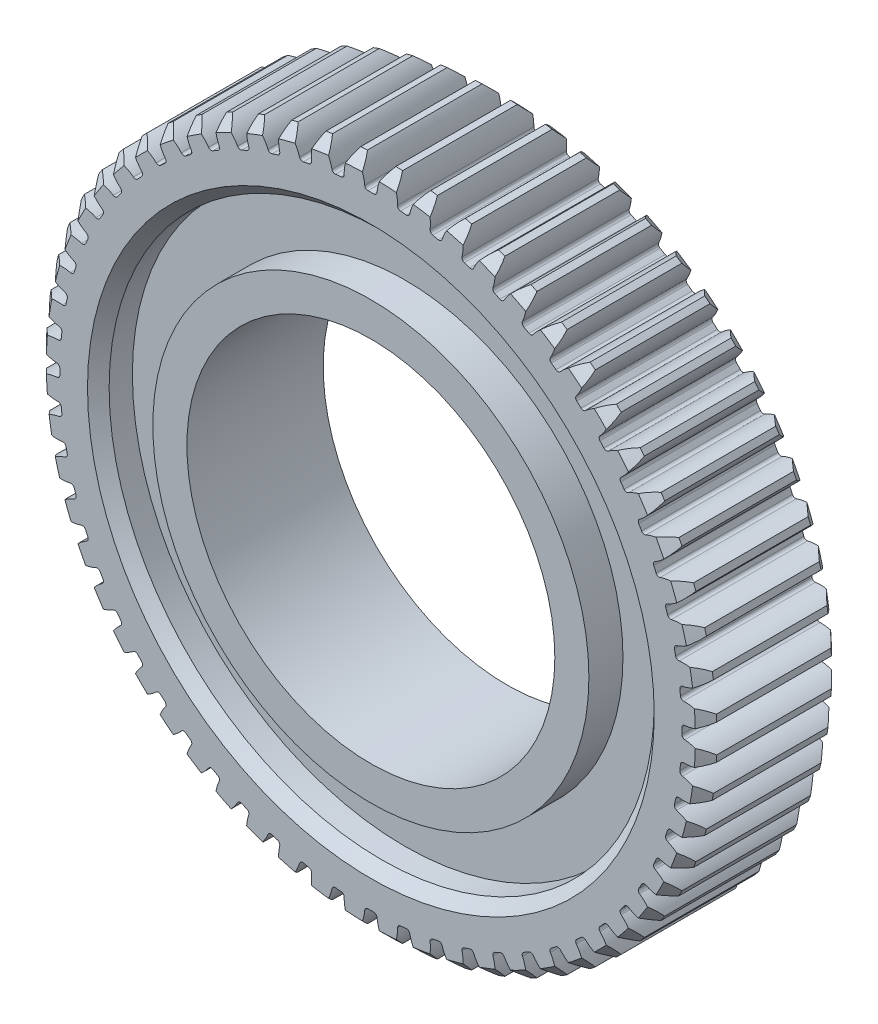
SolidWorks part; units mm, degrees
ref_plane "Front Plane" through (0, 0, 0) normal (0, 0, 1) x (1, 0, 0)
ref_plane "Top Plane" through (0, 0, 0) normal (0, 1, 0) x (1, 0, 0)
ref_plane "Right Plane" through (0, 0, 0) normal (1, 0, 0) x (0, 0, -1)
sketch "Sketch1" plane through (0, 0, 0) normal (0, 0, 1) x (1, 0, 0)
  circle A0 centre (0, 0) radius 47.625 construction
  circle A1 centre (0, 0) radius 49.2125
  dimension "D1" = 95.25
  dimension "D2" = 98.425
extrude "Boss-Extrude1" add sketch "Sketch1" along normal mid plane 20
sketch "Sketch2" plane through (0, 0, 0) normal (0, 0, 1) x (1, 0, 0)
  line L0 (0, 49.2125) -> (0, 0) construction
  line L1 (0, 0) -> (5.1441, 48.9429) construction
  line L2 (0, 0) -> (2.5756, 49.1451) construction
  line L3 (0, 0) -> (-0.8785, 45.6322) construction
  line L4 (-1.2467, 47.6087) -> (1.2467, 47.6087) construction
  line L5 (1.2467, 47.6087) -> (3.7366, 47.4782) construction
  line L6 (-1.8182, 49.1789) -> (0, 44.1835) construction
  circle A0 centre (0, 0) radius 46.0375 construction
  arc A2 (0.8785, 45.6322) -> (-0.8785, 45.6322) centre (0, 0) ccw
  circle A3 centre (0, 0) radius 49.2125 construction
  arc A4 (-0.8785, 45.6322) -> (-2.087, 49.1682) centre (-7.0009, 45.5143) ccw
  arc A5 (0.8785, 45.6322) -> (2.087, 49.1682) centre (7.0009, 45.5143) cw
  circle A6 centre (0, 0) radius 47.625 construction
  circle A7 centre (0, 0) radius 49.2125 construction
  arc A8 (5.1441, 48.9429) -> (-2.087, 49.1682) centre (0, 0) ccw
  dimension "D1" = 6
  dimension "D2" = 3.175
  dimension "D3" = 3.5719
  dimension "D4" = 20
extrude "Cut-Extrude1" cut sketch "Sketch2" against normal through all both and the other way through all contours A5 A8 A4 A2 region at (0, 47.6957, 0)
chamfer "Chamfer1" distance 1.5875 2 edges at (0, -49.2125, 10) (0, -49.2125, -10)
fillet "Fillet1" radius 0.4762 2 edges at (0.8785, 45.6322, 0) (-0.8785, 45.6322, 0)
pattern_circular "CirPattern1" count 60 over 360 about axis through (0, 0, 10) along (0, 0, -1) of "Fillet1", "Cut-Extrude1" reverse direction yes
sketch "Sketch3" plane through (0, 0, 10) normal (0, 0, 1) x (1, 0, 0)
  circle A0 centre (0, 0) radius 27
  dimension "D1" = 54
extrude "Cut-Extrude2" cut sketch "Sketch3" against normal blind 54
sketch "Sketch4" plane through (0, 0, 10) normal (0, 0, 1) x (1, 0, 0)
  circle A0 centre (0, 0) radius 27
  circle A1 centre (0, 0) radius 32
  circle A2 centre (0, 0) radius 40
  dimension "D1" = 80
  dimension "D2" = 54
  dimension "D3" = 5
extrude "Cut-Extrude3" cut sketch "Sketch4" against normal blind 5 contours A2 A1 region at (-38.8686, 0, 10)
mirror "Mirror1" about plane through (0, 0, 0) normal (0, 0, 1) of "Cut-Extrude3"
chamfer "Chamfer2" distance 1.5875 2 edges at (40, 0, -10) (40, 0, 10)
scale "Scale2" scale about centroid uniform scaling yes scale factor 0.259094
equation "\"Module\"= 1.5875mm"
equation "\"Num of Teeth\"= 60"
equation "\"Pressure Angle\"= 20"
equation "\"D1@Sketch1\"=\"Module\"*\"Num of Teeth\""
equation "\"D2@Sketch1\"=(\"Num of Teeth\" + 2 ) * \"Module\""
equation "\"D1@Sketch2\"=360 / \"Num of Teeth\""
equation "\"D2@Sketch2\"= \"Module\"*2"
equation "\"D3@Sketch2\"=\"Module\" *if(\"Module\" = > 1.25,2.25,2.4)"
equation "\"D4@Sketch2\"=\"Pressure Angle\""
equation "\"D1@Fillet1\"=.3 * \"Module\""
equation "\"D1@CirPattern1\"=\"Num of Teeth\""
equation "\"D1@Chamfer1\"=\"Module\""
equation "\"Hub\"=54"
equation "\"D1@Sketch3\"=\"Hub\""
equation "\"D2@Sketch4\"=54"
equation "\"D1@Chamfer2\"=\"Module\""
